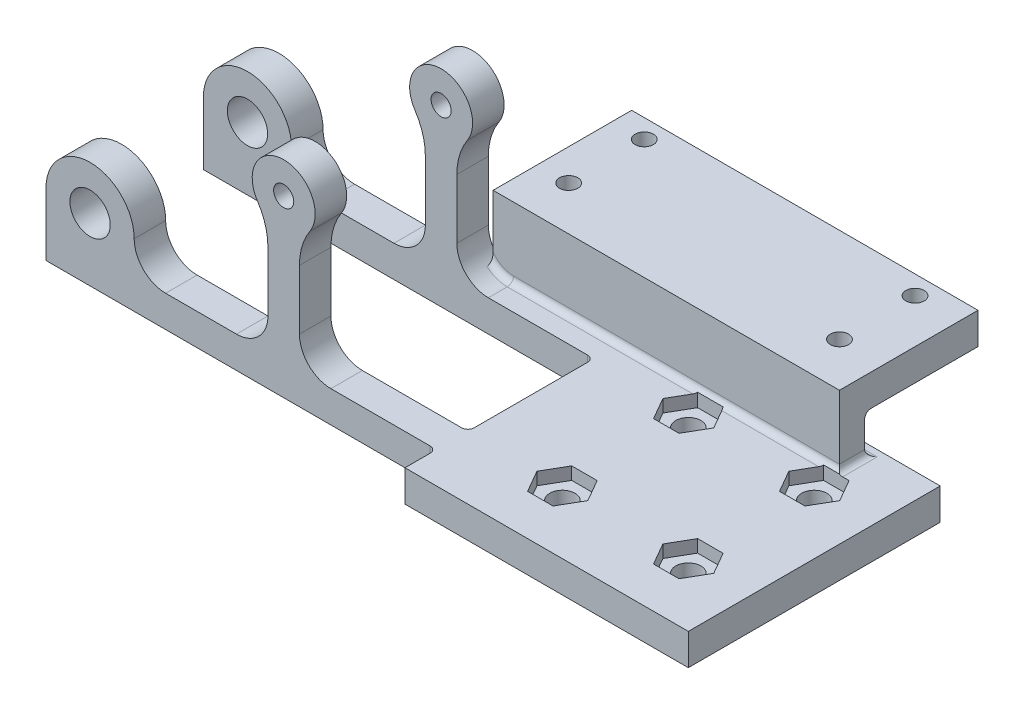
SolidWorks part; units mm, degrees
material "ABS"
ref_plane "Front Plane" through (0, 0, 0) normal (0, 0, 1) x (1, 0, 0)
ref_plane "Top Plane" through (0, 0, 0) normal (0, 1, 0) x (1, 0, 0)
ref_plane "Right Plane" through (0, 0, 0) normal (1, 0, 0) x (0, 0, -1)
sketch "SHAFT LOCATIONS" plane through (0, 0, 0) normal (0, 0, 1) x (1, 0, 0)
  line L0 (-80, 10) -> (-49.2561, 27.75) construction
  line L1 (-49.2561, 27.75) -> (-17.8635, 36.1616) construction
  line L2 (36.4641, 0) -> (-36.4641, 0) construction
  circle A0 centre (-80, 10) radius 3.2
  circle A1 centre (-49.2561, 27.75) radius 1.6
  circle A2 centre (-17.8635, 36.1616) radius 1.6
  dimension "D1" = 6.4
  dimension "D4" = 3.2
  dimension "D5" = 3.2
  dimension "D2" = 80
  dimension "D3" = 10
  dimension "D6" = 35.5
  dimension "D7" = 32.5
  dimension "D8" = 30
  dimension "D9" = 15
ref_plane "LEFT LEG Wall" through (0, 0, 10) normal (0, 0, 1) x (1, 0, 0)
sketch "Sketch1" plane through (0, 0, 0) normal (0, 1, 0) x (1, 0, 0)
  line L1 (-25, 20) -> (20, 20)
  line L2 (-25, 20) -> (-25, -20)
  line L3 (-25, -20) -> (20, -20)
  line L4 (20, 20) -> (20, -20)
  dimension "D1" = 40
  dimension "D2" = 20
  dimension "D3" = 20
  dimension "D4" = 45
extrude "Connection_Base" add sketch "Sketch1" along normal blind 5
sketch "Sketch9" plane through (0, 0, 10) normal (0, 0, 1) x (1, 0, 0)
  line L0 (-25, 0) -> (20, 0) construction
  line L5 (-51.7561, 5) -> (-73, 5)
  line L11 (0, 0) -> (-87, 0)
  line L12 (0, 0) -> (0, 5)
  line L18 (0, 5) -> (-46.7561, 5)
  line L20 (-73, 5) -> (-73, 10)
  line L22 (-87, 0) -> (-87, 10)
  line L25 (-51.7561, 23.4199) -> (-51.7561, 5)
  line L27 (-46.7561, 23.4199) -> (-46.7561, 5)
  circle A3 centre (-80, 10) radius 3.2 construction
  circle A6 centre (-80, 10) radius 3.2
  circle A7 centre (-49.2561, 27.75) radius 1.6 construction
  circle A8 centre (-49.2561, 27.75) radius 1.6
  arc A10 (-46.7561, 23.4199) -> (-51.7561, 23.4199) centre (-49.2561, 27.75) ccw
  arc A11 (-73, 10) -> (-87, 10) centre (-80, 10) ccw
  point P19 (-54.9111, 2.5)
  point P28 (-38.4151, 28.2356)
  point P32 (-49.2561, 14.2618)
  dimension "D1" = 7
  dimension "D5" = 5
  dimension "D2" = 5
  dimension "D3" = 5
  dimension "D4" = 2.5
extrude "LEFT_LEG" add sketch "Sketch9" along normal blind 5
fillet "LEG_Fillet" radius 5 3 edges at (-51.7561, 5, 12.5) (-46.7561, 5, 12.5) (-73, 5, 12.5)
fillet "Hub_Fillet" radius 10 2 edges at (-51.7561, 23.4199, 12.5) (-46.7561, 23.4199, 12.5)
mirror "Mirror_RIGHT_LEG" about plane through (0, 0, 0) normal (0, 0, 1) of "Hub_Fillet", "LEFT_LEG", "LEG_Fillet"
sketch "Sketch2" plane through (0, 5, 0) normal (0, 1, 0) x (1, 0, 0)
  circle A0 centre (-10, 10) radius 2
  dimension "D1" = 4
  dimension "D2" = 10
  dimension "D3" = 10
extrude "Base_Conn_Hole" cut sketch "Sketch2" against normal through all
sketch "Sketch3" plane through (0, 5, 0) normal (0, 1, 0) x (1, 0, 0)
  line L0 (20, 20) -> (-25, 20) construction
  line L1 (-7.9793, 6.5) -> (-5.9585, 10)
  line L2 (-5.9585, 10) -> (-7.9793, 13.5)
  line L3 (-7.9793, 13.5) -> (-12.0207, 13.5)
  line L4 (-12.0207, 13.5) -> (-14.0415, 10)
  line L5 (-14.0415, 10) -> (-12.0207, 6.5)
  line L6 (-12.0207, 6.5) -> (-7.9793, 6.5)
  circle A0 centre (-10, 10) radius 3.5 construction
  dimension "D1" = 7
extrude "Base_Conn_Nut" cut sketch "Sketch3" against normal blind 2
pattern_linear "Base_Holes_Pattern" count 2 spacing 20 along (0, 0, 1) count 2 spacing 20 along (1, 0, 0) of "Base_Conn_Hole", "Base_Conn_Nut"
sketch "Sketch4" plane through (0, 5, 0) normal (0, 1, 0) x (1, 0, 0)
  line L0 (20, -20) -> (20, 20) construction
  line L1 (10, 14) -> (-45, 14)
  line L2 (10, 14) -> (10, 18)
  line L3 (10, 18) -> (-45, 18)
  line L4 (-45, 14) -> (-45, 18)
  line L6 (20, 20) -> (-25, 20) construction
  dimension "D1" = 10
  dimension "D2" = 4
  dimension "D3" = 55
  dimension "D4" = 2
extrude "Motor_Step" add sketch "Sketch4" along normal blind 6.16
sketch "Sketch5" plane through (0, 11.16, 0) normal (0, 1, 0) x (1, 0, 0)
  line L0 (10, 14) -> (10, 18) construction
  line L1 (-45, 14) -> (10, 14)
  line L2 (-45, 14) -> (-45, 36)
  line L3 (-45, 36) -> (10, 36)
  line L4 (10, 14) -> (10, 36)
  dimension "D1" = 22
extrude "Motor_Shelf" add sketch "Sketch5" along normal blind 5
hole_wizard "Motor_M3.5x0.6 Tapped Hole1" positions "Sketch7" profile "Sketch8" tap size "M3.5x0.6" standard "ANSI Metric" end condition through all
sketch "Sketch7" plane through (0, 16.16, 0) normal (0, 1, 0) x (1, 0, 0)
  line L0 (10, 14) -> (10, 36) construction
  line L1 (10, 36) -> (-45, 36) construction
  point P0 (3, 21)
  point P2 (3, 33)
  point P4 (-40, 33)
  point P6 (-40, 21)
  dimension "D1" = 12
  dimension "D2" = 43
  dimension "D3" = 7
  dimension "D4" = 3
sketch "Sketch8" plane through (3, 16.16, -21) normal (1, 0, 0) x (0, 0, 1)
  line L0 (0, 0) -> (0, 16.16)
  line L1 (0, 16.16) -> (1.45, 16.16)
  line L2 (1.45, 16.16) -> (1.45, 0)
  line L5 (1.45, 0) -> (0, 0)
  line L11 (0, -6.35) -> (0, 107.95) construction
  dimension "Thru Tap Drill Dia." = 2.9
  dimension "Thru Tap Drill Depth" = 16.16
cosmetic thread "Hole Thread1" parameters "D2"=3.5
cosmetic thread "Hole Thread2" parameters "D2"=3.5
cosmetic thread "Hole Thread3" parameters "D2"=3.5
cosmetic thread "Hole Thread4" parameters "D2"=3.5
fillet "Small_Internal_Fillets" radius 1 8 edges at (-17.5, 11.16, -18) (-15.878, 5, -14) (-7.5, 5, -18) (10, 5, -16) (-43.4846, 5.3083, -14) (-25, 2.5, 10) (-25, 2.5, -10) (-25, 2.5, 15)
equation "\"D4@Sketch9\"=\"D3@Sketch9\"/2"
